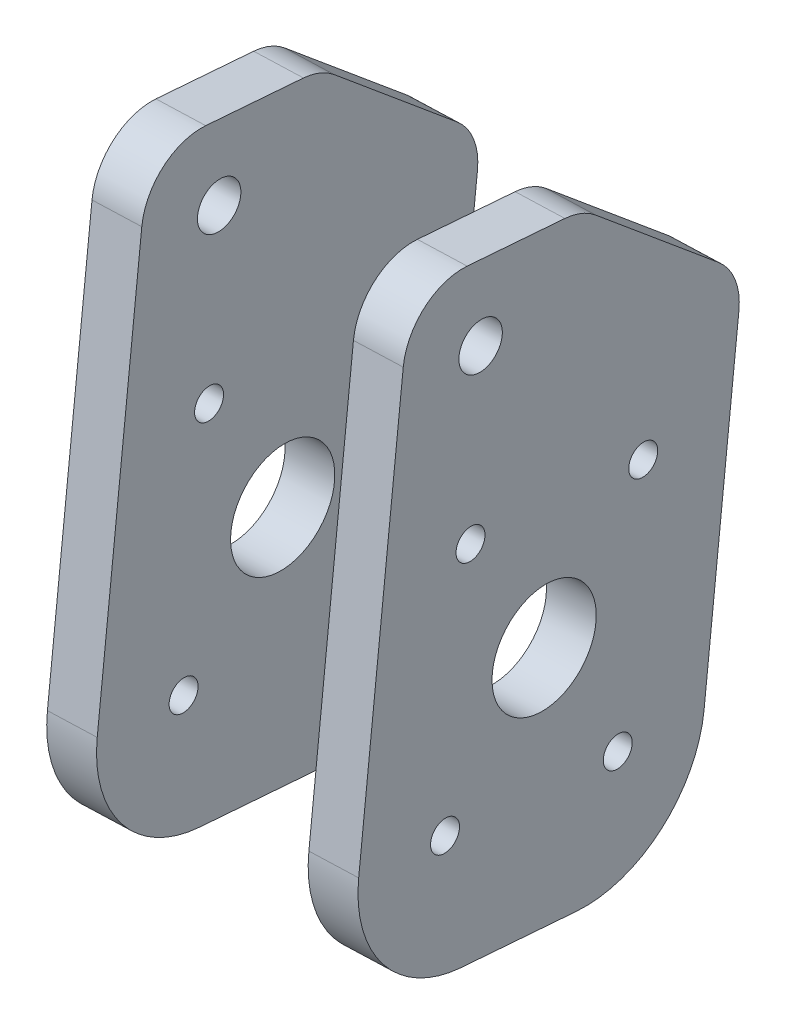
SolidWorks part; units mm, degrees
material "7075-T6, Plate (SS)"
ref_plane "Ground Plane" through (0, 0, 0) normal (0, 0, 1) x (1, 0, 0)
ref_plane "Side Plane" through (0, 0, 0) normal (0, 1, 0) x (1, 0, 0)
ref_plane "Rear Axle Centerline" through (0, 0, 0) normal (1, 0, 0) x (0, 0, -1)
sketch "Chassis Side View" plane through (0, 0, 0) normal (0, 1, 0) x (1, 0, 0)
  line L0 (0, -381) -> (2300, -381) construction
  line L1 (1150, -381) -> (1150, -856.742)
  line L2 (2150, -381) -> (2150, -1062.9307) construction
  line L3 (-753.0356, 0) -> (753.0356, 0) construction
  line L4 (2450, -381) -> (2450, -1062.9307) construction
  dimension "D1" = 2300
  dimension "D2" = 475.742
  dimension "D3" = 1150
  dimension "D4" = 381
  dimension "D5" = 150
  dimension "D6" = 150
ref_plane "Front Axle Centerline" through (2300, 0, 0) normal (1, 0, 0) x (0, 0, -1)
sketch "Front Wheel Assy Constraints" plane through (2300, 0, 0) normal (1, 0, 0) x (0, 0, -1)
  line L0 (0, 727.5) -> (0, 822.5)
  line L1 (0, 822.5) -> (-271.78, 822.5)
  line L2 (-271.78, 822.5) -> (-551.18, 822.5)
  line L3 (-551.18, 822.5) -> (-551.18, 727.5)
  line L4 (-551.18, 775) -> (0, 775) construction
  line L5 (-271.78, 822.5) -> (-271.78, 775) construction
  line L6 (-551.18, 727.5) -> (-445.4516, 727.5)
  line L7 (-445.4516, 727.5) -> (-445.4516, 798.5)
  line L8 (-445.4516, 798.5) -> (-105.7284, 798.5)
  line L9 (-105.7284, 798.5) -> (-105.7284, 727.5)
  line L10 (-105.7284, 727.5) -> (0, 727.5)
  line L11 (0, 0) -> (-673.9047, 0) construction
  line L13 (0, 753.0356) -> (0, -753.0356) construction
  dimension "D1" = 95
  dimension "D2" = 279.4
  dimension "D3" = 271.78
  dimension "D4" = 23.5
  dimension "D5" = 1550
sketch "Front Sus Front View" plane through (2300, 0, 0) normal (1, 0, 0) x (0, 0, -1)
  line L0 (0, 775) -> (0, 768.65) construction
  line L1 (0, 753.0356) -> (0, -753.0356) construction
  line L2 (0, 768.65) -> (-762, 634.2888) construction
  line L3 (0, 768.65) -> (-745.3671, 768.65) construction
  line L4 (-366.7919, -1090.2477) -> (-525.9451, 520.8571) construction
  line L5 (-366.7919, -1090.2477) -> (-379.5678, 520.8571) construction
  line L6 (-366.7919, -1090.2477) -> (0, 775) construction
  line L7 (-525.9451, 520.8571) -> (-541, 673.2571)
  line L8 (-379.5678, 520.8571) -> (-381, 701.4694)
  line L9 (0, 0) -> (-152.4, 0) construction
  line L13 (-525.9451, 520.8571) -> (-379.5678, 520.8571) construction
  dimension "D1" = 6.35
  dimension "D2" = 10
  dimension "D3" = 152.4
  dimension "D4" = 1865.2477
  dimension "D7" = 541
  dimension "D8" = 153.1418
ref_plane "Fron Wheel Side View Plane" through (0, 775, 0) normal (0, 1, 0) x (1, 0, 0)
sketch "Front SVSA" plane through (0, 775, 0) normal (0, 1, 0) x (1, 0, 0)
  line L0 (2271.684, -676.7175) -> (2328.316, 133.1575)
  line L1 (2300, 0) -> (2300, -771.0839) construction
  line L2 (2300, 0) -> (-2450.054, -116.0888) construction
  line L3 (-2450.054, -116.0888) -> (2298.2335, -297.0415) construction
  line L4 (-753.0356, 0) -> (753.0356, 0) construction
  point P5 (2300, -271.78)
  dimension "D1" = 4
  dimension "D2" = 1.4
  dimension "D3" = 4750.054
sketch3d "Front Chassis Side Axes"
  line L0 (2300, 520.8571, 379.5678) -> (2300, 701.4694, 381) construction
  line L1 (2300, 520.8571, 525.9451) -> (2300, 673.2571, 541) construction
  line L2 (2300, 520.8571, 379.5678) -> (2300, 701.4694, 381) construction
  line L3 (2300, 520.8571, 525.9451) -> (2300, 673.2571, 541) construction
  line L4 (2300, 673.2571, 541) -> (2300, 775, 551.0507) construction
  line L5 (2300, 701.4694, 381) -> (2300, 775, 381.5831) construction
  line L6 (2300, 775, 0) -> (2300, 775, 771.0839) construction
  line L7 (-2450.054, 775, 116.0888) -> (2349.7917, 775, 555.6101) construction
  line L8 (-2450.054, 775, 116.0888) -> (2349.9221, 775, 384.3734) construction
  line L9 (2349.9221, 775, 384.3734) -> (2177.377, 520.8571, 372.714) construction
  line L10 (2349.7917, 775, 555.6101) -> (2225.4174, 520.8571, 519.1156) construction
  line L11 (2300, 520.8571, 525.9451) -> (2300, 520.8571, 519.1156) construction
  line L12 (2300, 520.8571, 519.1156) -> (2225.4174, 520.8571, 519.1156) construction
  line L13 (2598.7501, 520.8571, 553.3017) -> (1702.4998, 520.8571, 471.2321)
  line L14 (2300, 520.8571, 379.5678) -> (2300, 520.8571, 372.714) construction
  line L15 (2300, 520.8571, 372.714) -> (2177.377, 520.8571, 372.714) construction
  line L16 (2599.5325, 520.8571, 396.3095) -> (1700.935, 520.8571, 346.0843)
  dimension "D1" = 50
  dimension "D2" = 50
  dimension "D3" = 600
  dimension "D4" = 300
  dimension "D5" = 600
  dimension "D6" = 300
sketch3d "Front Left Control Arm"
  line L0 (2300, 520.8571, 379.5678) -> (2300, 701.4694, 381) construction
  line L2 (2300, 520.8571, 379.5678) -> (2300, 701.4694, 381) construction
  line L3 (2300, 520.8571, 525.9451) -> (2300, 673.2571, 541) construction
  line L4 (2598.7501, 520.8571, 553.3017) -> (1702.4998, 520.8571, 471.2321) construction
  line L5 (2599.5325, 520.8571, 396.3095) -> (1700.935, 520.8571, 346.0843) construction
  line L6 (2598.7501, 520.8571, 553.3017) -> (1702.4998, 520.8571, 471.2321) construction
  line L7 (2599.5325, 520.8571, 396.3095) -> (1700.935, 520.8571, 346.0843) construction
  line L8 (2450, 520.8571, 539.6806) -> (2280.5957, 673.2571, 539.2232)
  line L9 (2280.5957, 673.2571, 539.2232) -> (2150, 520.8571, 512.2097)
  line L10 (2300, 520.8571, 525.9451) -> (2300, 673.2571, 541) construction
  line L11 (2300, 673.2571, 541) -> (2280.5957, 673.2571, 539.2232) construction
  line L12 (2271.684, 775, 676.7175) -> (2328.316, 775, -133.1575) construction
  line L13 (2150, 0, 512.2097) -> (2150, 520.8571, 512.2097) construction
  line L14 (2292.3517, 701.4694, 380.5725) -> (2292.3517, 775, 381.1556) construction
  line L15 (2150, 0, 381) -> (2150, 0, 1062.9307) construction
  line L16 (2450, 0, 539.6806) -> (2450, 520.8571, 539.6806) construction
  line L17 (2450, 0, 381) -> (2450, 0, 1062.9307) construction
  line L18 (2450, 520.8571, 387.9517) -> (2292.3517, 701.4694, 380.5725)
  line L19 (2292.3517, 701.4694, 380.5725) -> (2150, 520.8571, 371.1838)
  line L20 (2300, 701.4694, 381) -> (2292.3517, 701.4694, 380.5725) construction
  line L21 (2450, 0, 387.9517) -> (2450, 520.8571, 387.9517) construction
  line L22 (2150, 0, 371.1838) -> (2150, 520.8571, 371.1838) construction
  line L23 (2280.5957, 673.2571, 539.2232) -> (2280.5957, 775, 549.2738) construction
sketch3d "Front Control Arm"
  line L0 (2450, 520.8571, 387.9517) -> (2292.3517, 701.4694, 380.5725) construction
  line L1 (2292.3517, 701.4694, 380.5725) -> (2150, 520.8571, 371.1838) construction
  line L2 (2280.5957, 673.2571, 539.2232) -> (2150, 520.8571, 512.2097) construction
  line L3 (2450, 520.8571, 539.6806) -> (2280.5957, 673.2571, 539.2232) construction
  line L4 (2450, 520.8571, 387.9517) -> (2292.3517, 701.4694, 380.5725)
  line L5 (2292.3517, 701.4694, 380.5725) -> (2150, 520.8571, 371.1838)
  line L6 (2280.5957, 673.2571, 539.2232) -> (2150, 520.8571, 512.2097)
  line L7 (2450, 520.8571, 539.6806) -> (2280.5957, 673.2571, 539.2232)
  line L8 (2450, -520.8571, 539.6806) -> (2280.5957, -673.2571, 539.2232)
  line L9 (2280.5957, -673.2571, 539.2232) -> (2150, -520.8571, 512.2097)
  line L10 (2292.3517, -701.4694, 380.5725) -> (2150, -520.8571, 371.1838)
  line L11 (2450, -520.8571, 387.9517) -> (2292.3517, -701.4694, 380.5725)
ref_plane "Max Droop Plane" through (0, 0, -25.4) normal (0, 0, 1) x (1, 0, 0)
sketch3d "Shock"
  line L0 (2292.3517, 701.4694, 380.5725) -> (2293.5626, 664.4705, 414.2387) construction
  line L1 (2300, 520.8571, 525.9451) -> (2298.2629, 520.8571, 544.9158) construction
  line L2 (2150, 520.8571, 512.2097) -> (2450, 520.8571, 539.6806) construction
  line L3 (2300, 520.8571, 525.9451) -> (2300, 230.5152, 525.9451) construction
  line L4 (2293.5626, 664.4705, 414.2387) -> (2298.2629, 520.8571, 544.9158)
  dimension "D1" = 50.038
  dimension "D2" = 19.05
sketch3d "Parametric Analysis"
  line L2 (2300, 822.5, 0) -> (2300, 822.5, 271.78) construction
  line L3 (2300.4137, 822.5, 271.7939) -> (2300.4137, 822.5, -88.8537) construction
  line L4 (2450, 520.8571, 387.9517) -> (2292.3526, 701.4695, 380.5568)
  line L5 (2292.3526, 701.4695, 380.5568) -> (2150, 520.8571, 371.1838)
  line L6 (2450, 520.8571, 539.6806) -> (2280.5972, 673.2586, 539.2077)
  line L7 (2280.5972, 673.2586, 539.2077) -> (2150, 520.8571, 512.2097)
  line L8 (2292.3517, 701.4694, 380.5725) -> (2300, 822.5, 271.78) construction
  line L9 (2450, 520.8571, 387.9517) -> (2292.3517, 701.4694, 380.5725) construction
  line L10 (2292.3517, 701.4694, 380.5725) -> (2150, 520.8571, 371.1838) construction
  line L11 (2450, 520.8571, 539.6806) -> (2280.5957, 673.2571, 539.2232) construction
  line L12 (2280.5957, 673.2571, 539.2232) -> (2150, 520.8571, 512.2097) construction
  line L13 (2280.5957, 673.2571, 539.2232) -> (2292.3517, 701.4694, 380.5725) construction
  line L14 (2300, 822.5, 271.78) -> (2280.5957, 673.2571, 539.2232) construction
  line L15 (2300, 822.5, 271.78) -> (2300.4132, 720.8156, 271.78) construction
  line L16 (2280.5972, 673.2586, 539.2077) -> (2300.4137, 822.5, 271.7939) construction
  line L17 (2300.4137, 822.5, 271.7939) -> (2292.3526, 701.4695, 380.5568) construction
  line L18 (2280.5972, 673.2586, 539.2077) -> (2292.3526, 701.4695, 380.5568) construction
  line L19 (2300.4137, 822.5, 271.7939) -> (2300.4137, 720.8148, 271.7641) construction
  line L23 (2292.3517, 701.4694, 380.5725) -> (2265.8007, 667.7821, 378.8214) construction
  line L30 (2265.8007, 667.7821, 378.8214) -> (2325.2406, 663.7898, 382.112) construction
  line L31 (2325.2406, 663.7898, 382.112) -> (2293.5626, 664.4705, 414.2387) construction
  line L32 (2292.3517, 701.4694, 380.5725) -> (2325.2406, 663.7898, 382.112) construction
  line L33 (2293.5626, 664.4705, 414.2387) -> (2265.8007, 667.7821, 378.8214) construction
  line L34 (2292.3526, 701.4695, 380.5568) -> (2293.5633, 664.4722, 414.2247) construction
  line L35 (2292.3517, 701.4694, 380.5725) -> (2293.5626, 664.4705, 414.2387) construction
  line L39 (2300.4137, 822.5, 271.7939) -> (2300.4137, 822.5798, 0.014)
  line L40 (2300.4137, 822.5798, 0.014) -> (2300.4137, 727.5798, -0.014)
  line L41 (2300, 727.5, 0) -> (2300, 822.5, 0) construction
  line L42 (2298.2629, 520.8571, 544.9158) -> (2293.5633, 664.4722, 414.2247)
  point P5 (2300.4137, 775.0798, 0)
  dimension "D1" = 25.4
  dimension "D2" = 194.2357
  dimension "D3" = 0.0798
  dimension "D4" = 0.017
sketch3d "3DSketch1"
  line L0 (2293.5626, 664.4705, 414.2387) -> (2298.2629, 520.8571, 544.9158) construction
  line L1 (2280.5972, 673.2586, 539.2077) -> (2150, 520.8571, 512.2097) construction
  line L2 (2450, 520.8571, 539.6806) -> (2280.5972, 673.2586, 539.2077) construction
  line L3 (2292.3526, 701.4695, 380.5568) -> (2150, 520.8571, 371.1838) construction
  line L4 (2450, 520.8571, 387.9517) -> (2292.3526, 701.4695, 380.5568) construction
  line L5 (2293.5626, 664.4705, 414.2387) -> (2298.2629, 520.8571, 544.9158)
  line L6 (2280.5972, 673.2586, 539.2077) -> (2150, 520.8571, 512.2097)
  line L7 (2450, 520.8571, 539.6806) -> (2280.5972, 673.2586, 539.2077)
  line L8 (2292.3526, 701.4695, 380.5568) -> (2150, 520.8571, 371.1838)
  line L9 (2450, 520.8571, 387.9517) -> (2292.3526, 701.4695, 380.5568)
  line L10 (2450, 520.8571, 539.6806) -> (2450, 470.0571, 539.6806) construction
  line L11 (2150, 520.8571, 512.2097) -> (2150, 470.0571, 512.2097) construction
  line L12 (2298.2629, 520.8571, 544.9158) -> (2298.2629, 470.0571, 544.9158) construction
  line L13 (2450, 520.8571, 387.9517) -> (2450, 470.0571, 387.9517) construction
  line L14 (2150, 520.8571, 371.1838) -> (2150, 470.0571, 371.1838) construction
  line L15 (2150, -520.8571, 512.2097) -> (2150, -470.0571, 512.2097) construction
  line L16 (2298.2629, -520.8571, 544.9158) -> (2298.2629, -470.0571, 544.9158) construction
  line L17 (2450, -520.8571, 539.6806) -> (2450, -470.0571, 539.6806) construction
  line L18 (2293.5626, -664.4705, 414.2387) -> (2298.2629, -520.8571, 544.9158)
  line L19 (2280.5972, -673.2586, 539.2077) -> (2150, -520.8571, 512.2097)
  line L20 (2450, -520.8571, 539.6806) -> (2280.5972, -673.2586, 539.2077)
  line L21 (2450, -520.8571, 387.9517) -> (2450, -470.0571, 387.9517) construction
  line L22 (2150, -520.8571, 371.1838) -> (2150, -470.0571, 371.1838) construction
  line L23 (2292.3526, -701.4695, 380.5568) -> (2150, -520.8571, 371.1838)
  line L24 (2450, -520.8571, 387.9517) -> (2292.3526, -701.4695, 380.5568)
  line L27 (2300, 775, 551.18) -> (2300, 775, 0) construction
  dimension "D1" = 50.8
  dimension "D2" = 304.9478
  dimension "D3" = 544.9185
ref_plane "Plane1" through (0, 718.612, 0) normal (0, 1, 0) x (1, 0, 0)
sketch "Sketch1" plane through (0, 718.612, 0) normal (0, 1, 0) x (1, 0, 0)
  line L0 (2300, 0) -> (2300, -551.18) construction
  line L1 (2300, 0) -> (2300, -673.9047) construction
  line L2 (-753.0356, 0) -> (753.0356, 0) construction
  line L3 (2300, -275.59) -> (2280.5957, -539.2232) construction
  line L4 (2295.0737, -527.2852) -> (2266.1177, -527.2852)
  line L5 (2295.0737, -527.2852) -> (2319.6398, -484.4331)
  line L6 (2319.6398, -484.4331) -> (2343.1517, -404.3723)
  line L7 (2343.1517, -404.3723) -> (2343.1517, -356.7727)
  line L8 (2343.1517, -356.7727) -> (2320.6639, -270.2211)
  line L9 (2266.1177, -527.2852) -> (2241.5517, -484.4331)
  line L10 (2241.5517, -484.4331) -> (2241.5517, -356.7727)
  line L11 (2280.4102, -267.1009) -> (2241.5517, -356.7727)
  line L12 (2332.9917, -380.5725) -> (2251.7117, -380.5725) construction
  line L13 (2343.1517, -356.7727) -> (2241.5517, -356.7727) construction
  line L14 (2332.9917, -365.6119) -> (2251.7117, -365.6119)
  line L15 (2332.9917, -365.6119) -> (2332.9917, -395.5331)
  line L16 (2332.9917, -395.5331) -> (2251.7117, -395.5331)
  line L17 (2251.7117, -365.6119) -> (2251.7117, -395.5331)
  line L18 (2332.9917, -365.6119) -> (2251.7117, -395.5331) construction
  line L19 (2332.9917, -395.5331) -> (2251.7117, -365.6119) construction
  line L20 (2343.1517, -404.3723) -> (2241.5517, -404.3723) construction
  line L21 (2319.6398, -484.4331) -> (2241.5517, -484.4331) construction
  line L22 (2280.5957, -539.2232) -> (2280.5957, -527.2852) construction
  circle A0 centre (2300, -275.59) radius 15
  arc A1 (2320.6639, -270.2211) -> (2280.4102, -267.1009) centre (2300, -275.59) ccw
  arc A2 (2280.4102, -267.1009) -> (2320.6639, -270.2211) centre (2300, -275.59) ccw construction
  point P21 (2292.3517, -380.5725)
  point P30 (2292.3517, -380.5725)
  dimension "D1" = 30
  dimension "D2" = 42.7
  dimension "D3" = 81.28
  dimension "D4" = 29.9212
  dimension "D5" = 10.16
  dimension "D6" = 10.16
  dimension "D7" = 8.8392
  dimension "D8" = 8.8392
  dimension "D9" = 11.938
  dimension "D10" = 28.956
  dimension "D11" = 88.9
ref_axis "Axis1" through (2270.4507, 648.9089, 676.1444) along (0.0728, 0.1746, -0.9819)
ref_plane "Plane2" through (2275.719, 0, -81.8538) normal (-0.9994, 0, 0.0359) x (0.0242, -0.7394, 0.6728)
sketch "Sketch2" plane through (2275.719, 0, -81.8538) normal (-0.9994, 0, 0.0359) x (0.0242, -0.7394, 0.6728)
  line L0 (137.3825, 763.0465) -> (34.6465, 837.7079)
  line L3 (10.3969, 761.1341) -> (92.5856, 701.4049)
  line L4 (92.5856, 701.4049) -> (137.3825, 763.0465)
  line L6 (64.5417, 792.433) -> (42.1433, 761.6122) construction
  line L13 (34.6465, 837.7079) -> (12.2481, 806.8871)
  line L14 (12.2481, 806.8871) -> (10.3969, 761.1341)
  line L16 (64.5417, 792.433) -> (83.2376, 731.7476) construction
  line L17 (42.1433, 761.6122) -> (105.6361, 762.5684) construction
  circle A0 centre (37.1133, 814.4096) radius 4.7625
  circle A1 centre (64.5417, 792.433) radius 3.175
  circle A2 centre (105.6361, 762.5684) radius 3.175
  circle A3 centre (83.2376, 731.7476) radius 3.175
  circle A4 centre (42.1433, 761.6122) radius 3.175
  circle A12 centre (73.8897, 762.0903) radius 11.43
  point P28 (75.0078, 775.7838)
  dimension "D5" = 9.525
  dimension "D6" = 6.35
  dimension "D7" = 6.35
  dimension "D8" = 6.35
  dimension "D9" = 6.35
  dimension "D2" = 101.6
  dimension "D3" = 76.2
  dimension "D4" = 127
  dimension "D10" = 38.1
  dimension "D11" = 50.8
  dimension "D12" = 19.05
  dimension "D13" = 19.05
  dimension "D14" = 25.4
  dimension "D15" = 25.4
  dimension "D16" = 19.05
  dimension "D17" = 19.05
extrude "Boss-Extrude1" add sketch "Sketch2" against normal mid plane 63.5
fillet "Fillet1" radius 25.4 2 edges at (2296.6018, 403.7598, 498.7347) (2299.3242, 412.1363, 574.4239)
fillet "Fillet3" radius 12.7 3 edges at (2296.2003, 504.744, 487.5732) (2297.4612, 534.1784, 522.6275) (2298.8224, 538.3666, 560.4721)
sketch "Sketch3" plane through (-1.3334, 335.4037, -37.071) normal (0.004, -0.9939, 0.1099) x (1, 0.004, -0.0002)
  line L0 (2276.4946, 540.348) -> (2319.6467, 538.7959)
  line L1 (2329.8001, 538.4307) -> (2266.3411, 540.7132) construction
  line L2 (2319.6467, 538.7959) -> (2322.3857, 614.9467)
  line L3 (2332.5391, 614.5815) -> (2269.0801, 616.864) construction
  line L4 (2322.3857, 614.9467) -> (2279.2336, 616.4988)
  line L5 (2279.2336, 616.4988) -> (2276.4946, 540.348)
  line L8 (2267.2541, 566.0968) -> (2268.1671, 591.4804) construction
  line L9 (2330.7131, 563.8143) -> (2331.6261, 589.1979) construction
  dimension "D1" = 10.16
  dimension "D2" = 10.16
extrude "Cut-Extrude1" cut sketch "Sketch3" against normal through all and the other way through all
equation "\"wheelbase\"= 2.3m"
equation "\"track_front_outer\"= 1.55m"
equation "\"cg_h\"= 18.73in"
equation "\"cg_b\"= \"wheelbase\" / 2"
equation "\"chassis_ride_height\"= 15in"
equation "\"hub_offset\"= 23.5mm"
equation "\"tire_radius\"= 11in"
equation "\"tire_radius_loaded\"= 10.7in"
equation "\"tire_width\"= 95mm"
equation "\"static_camber\"= 0deg"
equation "\"caster_static\"= 4deg"
equation "\"control_arm_ratio\"= 0.95"
equation "\"roll_center_height\"= 6in"
equation "\"scrub_radius\"= 0.25in"
equation "\"camber_change_rate\"= 0.5deg'per inch of travel"
equation "\"fvsa_length\"= atn ( 1 / \"camber_change_rate\" )"
equation "\"svsa_length\"= 2.5 * \"wheelbase\""
equation "\"svsa_height\"= 1"
equation "\"anti_squat_rear\"= 0.15"
equation "\"front_brakes\"= .75"
equation "\"anti_dive_front\"= 0.1"
equation "\"D1@Chassis Side View\" = \"wheelbase\""
equation "\"D2@Chassis Side View\" = \"cg_h\""
equation "\"D3@Chassis Side View\" = \"cg_b\""
equation "\"D4@Chassis Side View\" = \"chassis_ride_height\""
equation "\"D1@Front Axle Centerline\"=\"wheelbase\""
equation "\"D1@Front Wheel Assy Constraints\" = \"tire_width\""
equation "\"D2@Front Wheel Assy Constraints\" = \"tire_radius\""
equation "\"D3@Front Wheel Assy Constraints\" = \"tire_radius_loaded\""
equation "\"D4@Front Wheel Assy Constraints\" = \"hub_offset\""
equation "\"D1@Front Sus Front View\" = \"scrub_radius\""
equation "\"static_kingpin\"= 10deg"
equation "\"D2@Front Sus Front View\" = \"static_kingpin\""
equation "\"D3@Front Sus Front View\" = \"roll_center_height\""
equation "\"D6@Front Sus Front View\" = \"chassis_ride_height\""
equation "\"D7@Front Sus Front View\"=\"chassis_ride_height\" + 160mm"
equation "\"D1@Front SVSA\" = \"caster_static\""
equation "\"D4@Front Sus Front View\"=\"fvsa_length\"+10"
equation "\"D5@Front Wheel Assy Constraints\"=\"track_front_outer\""
equation "\"phi_front\"= atn ( \"anti_dive_front\" / \"front_brakes\" * \"cg_h\" / \"wheelbase\" )"
equation "\"anti_lift_rear\"= 0.1"
equation "\"a\"= 0"
